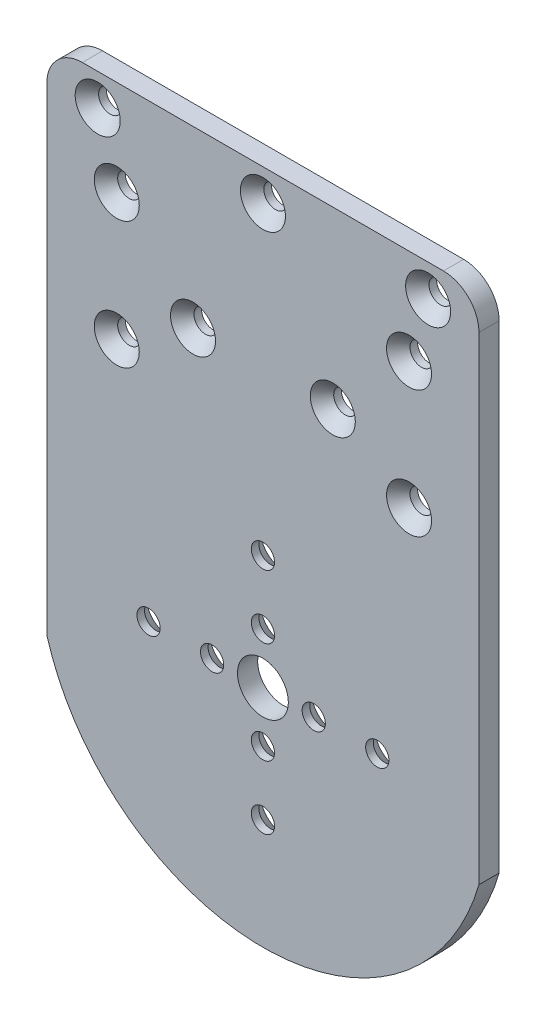
SolidWorks part; units mm, degrees
material "6061-T6 (SS)"
ref_plane "Front" through (0, 0, 0) normal (0, 0, 1) x (1, 0, 0)
ref_plane "Top" through (0, 0, 0) normal (0, 1, 0) x (1, 0, 0)
ref_plane "Right" through (0, 0, 0) normal (1, 0, 0) x (0, 0, -1)
ref_axis "side-side" through (80.9, 0, 0) along (-1, 0, 0)
ref_axis "up-down" through (0, 50, 0) along (0, -1, 0)
ref_axis "front-back" through (0, 0, -80.9) along (0, 0, 1)
sketch "Sketch3" plane through (0, 0, 0) normal (0, 0, 1) x (1, 0, 0)
  line L6 (51.5425, 86.8059) -> (50.8717, 77.6651) construction
  line L7 (43.9617, 91.9573) -> (51.5425, 86.8059) construction
  line L8 (35.7101, 87.9679) -> (43.9617, 91.9573) construction
  line L9 (35.0392, 78.827) -> (35.7101, 87.9679) construction
  line L10 (42.62, 73.6756) -> (35.0392, 78.827) construction
  line L11 (50.8717, 77.6651) -> (42.62, 73.6756) construction
  circle A1 centre (-33.9697, 52.0384) radius 3.556
  circle A3 centre (0, 114.3) radius 3.175
sketch "Sketch5" plane through (0, 0, 0) normal (0, 0, 1) x (1, 0, 0)
  line L0 (-32.07, 0) -> (-32.07, 40.8976) construction
  line L1 (-35.4, 0) -> (-35.4, 41.4898) construction
  line L3 (-17.5007, 36) -> (-20.2504, 40.7625)
  line L12 (29.5799, -5.0029) -> (33.9151, 20.6293)
  line L13 (34, 21.6405) -> (34, 55.2473)
  line L14 (32.224, 59.535) -> (9.8995, 81.8595)
  line L15 (-9.8995, 81.8595) -> (-32.224, 59.535)
  line L16 (-34, 55.2473) -> (-34, 21.6405)
  line L17 (-33.9151, 20.6293) -> (-29.5799, -5.0029)
  line L20 (3.5355, -21.2486) -> (21.2486, -3.5355)
  line L21 (21.2486, 3.5355) -> (3.5355, 21.2486)
  line L22 (-3.5355, 21.2486) -> (-21.2486, 3.5355)
  line L23 (-21.2486, -3.5355) -> (-3.5355, -21.2486)
  line L24 (-20.2504, 40.7625) -> (-25.7496, 40.7625)
  line L25 (-25.7496, 40.7625) -> (-28.4993, 36)
  line L26 (-28.4993, 36) -> (-25.7496, 31.2375)
  line L27 (-25.7496, 31.2375) -> (-20.2504, 31.2375)
  line L28 (-20.2504, 31.2375) -> (-17.5007, 36)
  line L29 (-17.5007, 56) -> (-20.2504, 60.7625)
  line L30 (-20.2504, 60.7625) -> (-25.7496, 60.7625)
  line L31 (-25.7496, 60.7625) -> (-28.4993, 56)
  line L32 (-28.4993, 56) -> (-25.7496, 51.2375)
  line L33 (-25.7496, 51.2375) -> (-20.2504, 51.2375)
  line L34 (-20.2504, 51.2375) -> (-17.5007, 56)
  circle A1 centre (18, 0) radius 1.3525
  circle A3 centre (0, -18) radius 1.3525
  circle A5 centre (3.5064, -7.1906) radius 1.3525
  arc A12 (-29.5799, -5.0029) -> (29.5799, -5.0029) centre (0, 0) ccw
  arc A13 (33.9151, 20.6293) -> (34, 21.6405) centre (27.9363, 21.6405) ccw
  arc A14 (34, 55.2473) -> (32.224, 59.535) centre (27.9363, 55.2473) ccw
  arc A15 (9.8995, 81.8595) -> (-9.8995, 81.8595) centre (0, 71.96) ccw
  arc A16 (-32.224, 59.535) -> (-34, 55.2473) centre (-27.9363, 55.2473) ccw
  arc A17 (-34, 21.6405) -> (-33.9151, 20.6293) centre (-27.9363, 21.6405) ccw
  circle A19 centre (0, 0) radius 35.4
  circle A20 centre (0, 0) radius 34 construction
  circle A21 centre (0, 0) radius 32.07 construction
  circle A22 centre (-23, 36) radius 4.7625 construction
  circle A23 centre (-23, 56) radius 4.7625 construction
  arc A28 (21.2486, -3.5355) -> (21.2486, 3.5355) centre (17.713, 0) ccw
  arc A29 (3.5355, 21.2486) -> (-3.5355, 21.2486) centre (0, 17.713) ccw
  arc A30 (-21.2486, 3.5355) -> (-21.2486, -3.5355) centre (-17.713, 0) ccw
  arc A31 (-3.5355, -21.2486) -> (3.5355, -21.2486) centre (0, -17.713) ccw
  point P5 (0, 0)
  point P49 (-23, 31.2375)
  point P57 (-23, 54.4266)
  point P59 (0, 0)
  point P67 (0, 0)
  dimension "D3" = 68
  dimension "D4" = 1.93
  dimension "D1" = 70.8
  dimension "D5" = 9.525
  dimension "D6" = 23
  dimension "D7" = 36
  dimension "D8" = 20
sketch "Sketch1" plane through (0, 0, 0) normal (0, 0, 1) x (1, 0, 0)
  line L0 (-34, 71) -> (-34, -9.857)
  line L2 (-34, 21.6405) -> (-34, 44.1661) construction
  line L3 (-34, 55.2473) -> (34, 55.2473) construction
  line L4 (34, 21.6405) -> (34, 55.2473) construction
  line L5 (0, -50) -> (0, 50) construction
  line L6 (-34, 55.2473) -> (-34, 21.6405) construction
  line L7 (-9.8995, 81.8595) -> (-32.224, 59.535) construction
  line L8 (32.224, 59.535) -> (9.8995, 81.8595) construction
  line L11 (0, 0) -> (0, 35.2592) construction
  line L14 (34, 71) -> (34, -9.857)
  line L15 (-34, 71) -> (34, 71)
  arc A0 (-34, -9.857) -> (34, -9.857) centre (0, 0) ccw
  circle A1 centre (0, 0) radius 4
  circle A2 centre (0, 8) radius 1.85 construction
  circle A3 centre (-8, 0) radius 1.85 construction
  circle A4 centre (0, -8) radius 1.85 construction
  circle A5 centre (8, 0) radius 1.85 construction
  circle A6 centre (0, 0) radius 8 construction
  arc A11 (9.8995, 81.8595) -> (-9.8995, 81.8595) centre (0, 71.96) ccw construction
  arc A12 (34, 55.2473) -> (32.224, 59.535) centre (27.9363, 55.2473) ccw construction
  circle A19 centre (23, 56) radius 1.85 construction
  circle A20 centre (23, 36) radius 1.85 construction
  circle A21 centre (-23, 56) radius 1.85 construction
  circle A22 centre (-23, 36) radius 1.85 construction
  circle A27 centre (0, 0) radius 35.4 construction
  circle A28 centre (-11, 43.5) radius 1.905 construction
  circle A29 centre (0, 43.5) radius 1.905 construction
  circle A30 centre (-11, 56) radius 1.905 construction
  circle A31 centre (-26, 66) radius 1.905 construction
  circle A32 centre (0, 66) radius 1.905 construction
  point P53 (0, 66.2168)
  point P54 (0, 0)
  point P55 (-23, 67.2345)
  point P56 (0, 0)
  point P57 (0, 0)
  point P59 (0, 0)
  point P60 (0, 0)
  point P61 (0, 0)
  point P62 (0, 41.5354)
  point P63 (0, 43.571)
  point P64 (0, 0)
  point P66 (-28.6299, 66)
  dimension "D3" = 8
  dimension "D4" = 3.7
  dimension "D5" = 16
  dimension "D6" = 35.4
  dimension "D9" = 11
  dimension "D10" = 43.5
  dimension "D11" = 8
  dimension "D7" = 3.81
  dimension "D1" = 68
  dimension "D2" = 15
  dimension "D8" = 5
extrude "Boss-Extrude1" add sketch "Sketch1" along normal blind 3.175
sketch "Sketch2" plane through (0, 0, 0) normal (0, 0, -1) x (-1, 0, 0)
  circle A1 centre (33.9697, 52.0384) radius 3.556
fillet "Fillet1" radius 5.588 2 edges at (-34, 71, 1.5875) (34, 71, 1.5875)
hole_wizard "CSK for #6 Flat Head Machine Screw1" positions "Sketch6" profile "Sketch7" countersink size "#6" standard "ANSI Inch" end condition through all
sketch "Sketch6" plane through (0, 0, 0) normal (0, 0, 1) x (1, 0, 0)
  circle A0 centre (0, 0) radius 8 construction
  circle A1 centre (0, 0) radius 18 construction
  point P0 (0, 8)
  point P2 (0, -8)
  point P4 (8, 0)
  point P6 (-8, 0)
  point P26 (18, 0)
  point P28 (0, -18)
  point P30 (-18, 0)
  point P32 (0, 18)
sketch "Sketch7" plane through (0, 8, 0) normal (1, 0, 0) x (0, 1, 0)
  line L0 (0, 0) -> (0, 3.175)
  line L1 (0, 3.175) -> (1.8288, 3.175)
  line L2 (1.8288, 3.175) -> (1.8288, 1.9723)
  line L3 (1.8288, 1.9723) -> (3.5433, 0)
  line L5 (3.5433, 0) -> (0, 0)
  line L6 (-1.8288, 1.9723) -> (-3.5433, 0) construction
  line L11 (0, -6.35) -> (0, 107.95) construction
  dimension "Thru Hole Dia." = 3.6576
  dimension "Thru Hole Depth" = 3.175
  dimension "Near C'Sink Dia." = 7.0866
  dimension "Near C'Sink Angle" = 82
hole_wizard "CSK for #6 Flat Head Machine Screw2" positions "Sketch8" profile "Sketch9" countersink size "#6" standard "ANSI Inch" end condition through all
sketch "Sketch8" plane through (0, 0, 3.175) normal (0, 0, -1) x (-1, 0, 0)
  line L0 (0, 0) -> (0, 93.8801) construction
  point P0 (-23, 36)
  point P3 (-23, 56)
  point P6 (0, 66)
  point P15 (11, 43.5)
  point P18 (23, 36)
  point P21 (23, 56)
  point P24 (26, 66)
  point P27 (-26, 66)
  point P31 (-11, 43.5)
  point P37 (0, 0)
  point P38 (0, 0)
  point P39 (0, 0)
  point P40 (0, 0)
sketch "Sketch9" plane through (23, 36, 3.175) normal (1, 0, 0) x (0, -1, 0)
  line L0 (0, 0) -> (0, 3.175)
  line L1 (0, 3.175) -> (1.8288, 3.175)
  line L2 (1.8288, 3.175) -> (1.8288, 1.9723)
  line L3 (1.8288, 1.9723) -> (3.5433, 0)
  line L5 (3.5433, 0) -> (0, 0)
  line L6 (-1.8288, 1.9723) -> (-3.5433, 0) construction
  line L11 (0, -6.35) -> (0, 107.95) construction
  dimension "Thru Hole Dia." = 3.6576
  dimension "Thru Hole Depth" = 3.175
  dimension "Near C'Sink Dia." = 7.0866
  dimension "Near C'Sink Angle" = 82
